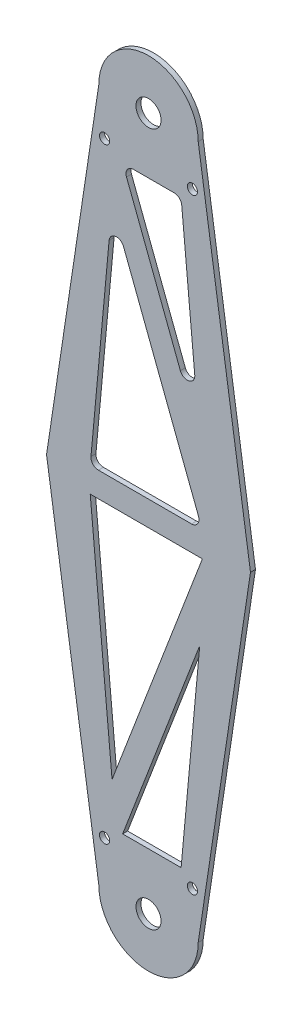
SolidWorks part; units mm, degrees
ref_plane "前视基准面" through (0, 0, 0) normal (0, 0, 1) x (1, 0, 0)
ref_plane "上视基准面" through (0, 0, 0) normal (0, 1, 0) x (1, 0, 0)
ref_plane "右视基准面" through (0, 0, 0) normal (1, 0, 0) x (0, 0, -1)
sketch "草图1" plane through (0, 0, 0) normal (0, 0, 1) x (1, 0, 0)
  line L0 (-28.7412, 13.5303) -> (29.1588, 13.5303) construction
  line L1 (17.8865, -108.392) -> (29.1588, 13.5303) construction
  line L18 (-17.4689, -108.392) -> (17.8865, -108.392) construction
  line L20 (-17.4689, -108.392) -> (29.1588, 13.5303) construction
  line L22 (-28.7412, 13.5303) -> (-17.4689, -108.392) construction
  line L23 (0.2088, -126.0697) -> (57.1498, -69.1287) construction
  line L41 (-40.8412, 168.1303) -> (41.2588, 168.1303) construction
  line L42 (-40.8412, -141.0697) -> (41.2588, -141.0697) construction
  line L43 (0.2088, 153.1303) -> (57.1498, 96.1893) construction
  line L44 (-19.7912, 153.1303) -> (-40.8412, 13.5303)
  line L46 (20.2088, 153.1303) -> (41.2588, 13.5303)
  line L60 (-10.2035, -103.392) -> (13.3274, -103.392)
  line L61 (-28.7412, 13.5303) -> (-17.4689, 135.4526) construction
  line L62 (-17.4689, 135.4526) -> (29.1588, 13.5303) construction
  line L63 (-23.2576, 18.5303) -> (-14.4673, 113.6066)
  line L64 (-14.4673, 113.6066) -> (21.8935, 18.5303)
  line L65 (21.8935, 18.5303) -> (-23.2576, 18.5303)
  line L66 (-17.4689, 135.4526) -> (17.8865, 135.4526) construction
  line L67 (17.8865, 135.4526) -> (29.1588, 13.5303) construction
  line L68 (-10.2035, 130.4526) -> (20.8298, 49.3066)
  line L69 (13.3274, 130.4526) -> (20.8298, 49.3066)
  line L70 (-10.2035, 130.4526) -> (13.3274, 130.4526)
  line L71 (29.1588, 13.5303) -> (-28.7412, 13.5303) construction
  line L72 (13.3274, -103.392) -> (20.8298, -22.246)
  line L73 (-10.2035, -103.392) -> (20.8298, -22.246)
  line L74 (21.8935, 8.5303) -> (-23.2576, 8.5303)
  line L75 (-14.4673, -86.546) -> (21.8935, 8.5303)
  line L76 (-23.2576, 8.5303) -> (-14.4673, -86.546)
  line L77 (20.2088, -126.0697) -> (41.2588, 13.5303)
  line L78 (-19.7912, -126.0697) -> (-40.8412, 13.5303)
  circle A0 centre (0.2088, 153.1303) radius 5.05
  circle A1 centre (0.2088, 153.1303) radius 25 construction
  circle A2 centre (17.8865, 135.4526) radius 2.05
  circle A3 centre (-17.4689, 135.4526) radius 2.05
  circle A4 centre (0.2088, 153.1303) radius 20 construction
  arc A5 (20.2088, 153.1303) -> (-19.7912, 153.1303) centre (0.2088, 153.1303) ccw
  circle A6 centre (0.2088, -126.0697) radius 20 construction
  circle A7 centre (0.2088, -126.0697) radius 25 construction
  arc A8 (20.2088, -126.0697) -> (-19.7912, -126.0697) centre (0.2088, -126.0697) cw
  circle A9 centre (-17.4689, -108.392) radius 2.05
  circle A10 centre (17.8865, -108.392) radius 2.05
  circle A11 centre (0.2088, -126.0697) radius 5.05
  point P16 (-30.7912, 13.5303)
  point P47 (31.2088, 13.5303)
  dimension "D10" = 10.1
  dimension "D13" = 50
  dimension "D14" = 4.1
  dimension "D16" = 5
  dimension "D15" = 15
  dimension "D17" = 5
extrude "凸台-拉伸1" add sketch "草图1" along normal blind 2
fillet "圆角1" radius 3 6 edges at (20.8298, 49.3066, 1) (21.8935, 18.5303, 1) (-23.2576, 18.5303, 1) (-14.4673, 113.6066, 1) (13.3274, 130.4526, 1) (-10.2035, 130.4526, 1)
